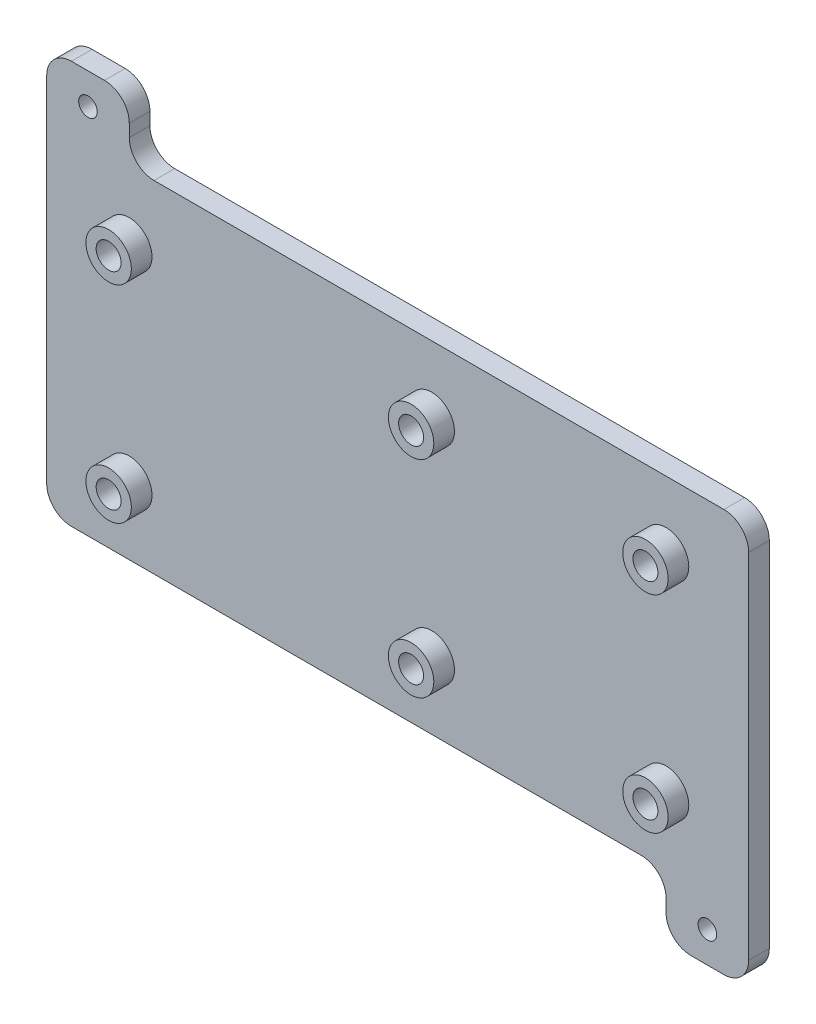
SolidWorks part; units mm, degrees
material "ABS"
ref_plane "X-Y Datum" through (0, 0, 0) normal (0, 0, 1) x (1, 0, 0)
ref_plane "X-Z Datum" through (0, 0, 0) normal (0, 1, 0) x (1, 0, 0)
ref_plane "Y-Z Datum" through (0, 0, 0) normal (1, 0, 0) x (0, 0, -1)
sketch "Sketch1" plane through (0, 0, 0) normal (0, 0, 1) x (1, 0, 0)
  line L1 (-70.0024, 29.9974) -> (70.0024, 29.9974) construction
  line L2 (-70.0024, 29.9974) -> (-70.0024, -29.9974) construction
  line L3 (-70.0024, -29.9974) -> (70.0024, -29.9974) construction
  line L4 (70.0024, 29.9974) -> (70.0024, -29.9974) construction
  line L5 (-70.0024, 29.9974) -> (70.0024, -29.9974) construction
  line L6 (-70.0024, -29.9974) -> (70.0024, 29.9974) construction
  line L7 (-85, 41.275) -> (85, 41.275)
  line L8 (-85, 41.275) -> (-85, -41.275)
  line L9 (-85, -41.275) -> (85, -41.275)
  line L10 (85, 41.275) -> (85, -41.275)
  line L11 (-85, 41.275) -> (85, -41.275) construction
  line L12 (-85, -41.275) -> (85, 41.275) construction
  point P0 (0, 0)
  point P6 (0, 0)
  dimension "D1" = 140.0048
  dimension "D2" = 59.9948
  dimension "D3" = 170
  dimension "D4" = 82.55
extrude "Boss-Extrude1" add sketch "Sketch1" along normal blind 5
sketch "Sketch2" plane through (0, 0, 5) normal (0, 0, 1) x (1, 0, 0)
  circle A0 centre (65, 25) radius 3.025
  circle A1 centre (65, -25) radius 3.025
  circle A2 centre (8.25, 25) radius 3.025
  circle A3 centre (8.25, -25) radius 3.025
  circle A4 centre (-65, 25) radius 3.025
  circle A5 centre (-65, -25) radius 3.025
  circle A6 centre (65, 25) radius 5.5
  circle A7 centre (8.25, 25) radius 5.5
  circle A8 centre (-65, 25) radius 5.5
  circle A9 centre (-65, -25) radius 5.5
  circle A10 centre (8.25, -25) radius 5.5
  circle A11 centre (65, -25) radius 5.5
  point P0 (65, -25)
  point P1 (65, 25)
  point P3 (8.25, 25)
  point P5 (8.25, -25)
  point P7 (-65, 25)
  point P9 (-65, -25)
  dimension "D1" = 6.05
  dimension "D2" = 11
extrude "Boss-Extrude2" add sketch "Sketch2" along normal blind 5
sketch "Sketch3" plane through (0, 0, 5) normal (0, 0, 1) x (1, 0, 0)
  line L0 (85, -41.275) -> (65, -56.275) construction
  line L1 (-85, 41.275) -> (-65, 41.275)
  line L2 (-85, 41.275) -> (-85, 56.275)
  line L3 (-85, 56.275) -> (-65, 56.275)
  line L4 (-65, 41.275) -> (-65, 56.275)
  line L5 (85, -41.275) -> (65, -41.275)
  line L6 (85, -41.275) -> (85, -56.275)
  line L7 (85, -56.275) -> (65, -56.275)
  line L8 (65, -41.275) -> (65, -56.275)
  line L9 (-65, 56.275) -> (-85, 41.275)
  point P10 (75, -48.775)
  point P11 (-75, 48.775)
  line M17 (85, 41.275) -> (-85, 41.275)
  line M19 (-85, -41.275) -> (85, -41.275)
  dimension "D1" = 15
  dimension "D2" = 20
  dimension "D3" = 15
  dimension "D4" = 20
extrude "Boss-Extrude3" add sketch "Sketch3" against normal blind 5 contours L9 L3 L2 | L4 L9 M17 | L0 L8 M19 | L6 L0 L7 region at (78.3333, -51.275, 5) region at (71.6667, -46.275, 5) region at (-71.6667, 46.275, 5) region at (-78.3333, 51.275, 5)
fillet "Fillet1" radius 6 8 edges at (65, -41.275, 2.5) (65, -56.275, 2.5) (85, -56.275, 2.5) (85, 41.275, 2.5) (-65, 41.275, 2.5) (-65, 56.275, 2.5) (-85, 56.275, 2.5) (-85, -41.275, 2.5)
hole_wizard "M4 Clearance Hole1" positions "Sketch4" profile "Sketch5" hole size "M4" standard "ANSI Metric" end condition through all
sketch "Sketch4" plane through (0, 0, 5) normal (0, 0, 1) x (1, 0, 0)
  point P0 (-75, 48.775)
  point P3 (75, -48.775)
sketch "Sketch5" plane through (-75, 48.775, 5) normal (1, 0, 0) x (0, -1, 0)
  line L0 (0, 0) -> (0, 5)
  line L1 (0, 5) -> (2.25, 5)
  line L2 (2.25, 5) -> (2.25, 0)
  line L5 (2.25, 0) -> (0, 0)
  line L11 (0, -6.35) -> (0, 107.95) construction
  dimension "Thru Hole Dia." = 4.5
  dimension "Thru Hole Depth" = 5
